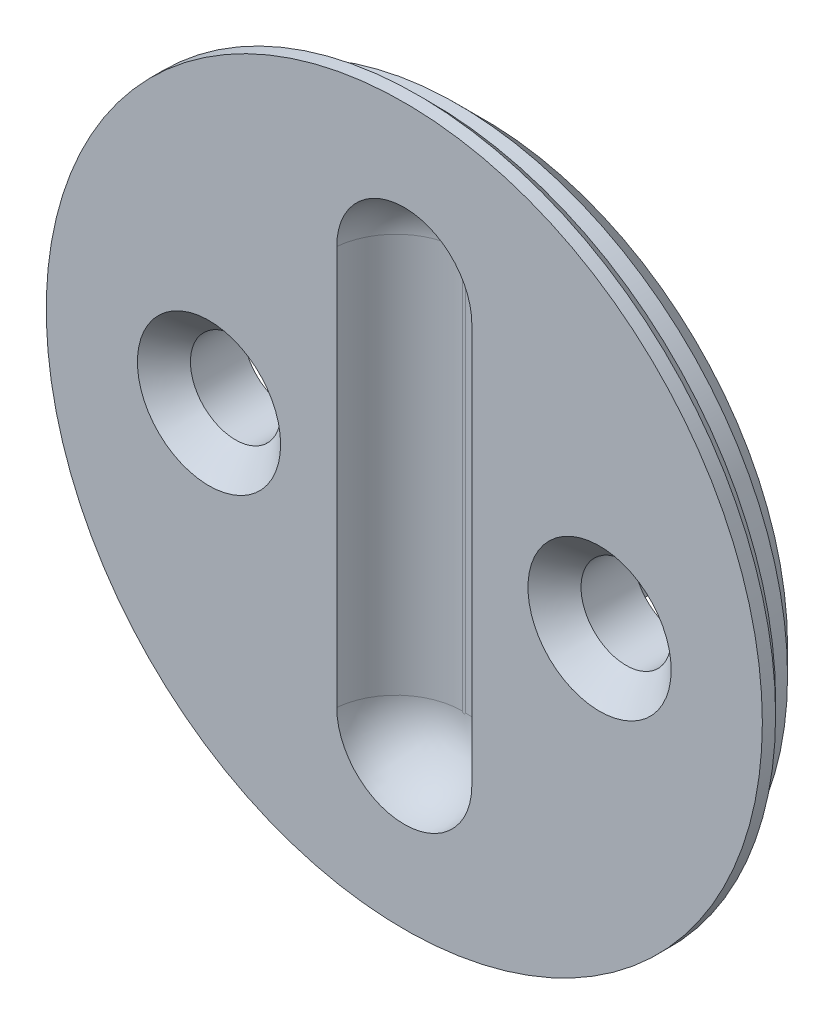
SolidWorks part; units mm, degrees
ref_plane "Front Plane" through (0, 0, 0) normal (0, 0, 1) x (1, 0, 0)
ref_plane "Top Plane" through (0, 0, 0) normal (0, 1, 0) x (1, 0, 0)
ref_plane "Right Plane" through (0, 0, 0) normal (1, 0, 0) x (0, 0, -1)
sketch "Sketch1" plane through (0, 0, 0) normal (0, 0, 1) x (1, 0, 0)
  line L0 (0, 9.3188) -> (0, -6.9028) construction
  circle A0 centre (0, 0) radius 12.45
  circle A1 centre (-7.363, 0) radius 1.7
  circle A2 centre (7.363, 0) radius 1.7
  dimension "D2" = 24.9
  dimension "D3" = 3.4
  dimension "D1" = 14.726
extrude "Boss-Extrude1" add sketch "Sketch1" against normal blind 2
sketch "Sketch2" plane through (0, 0, -2) normal (0, 0, -1) x (-1, 0, 0)
  line L1 (-3.85, 3.35) -> (3.85, 3.35)
  line L2 (-3.85, 3.35) -> (-3.85, -3.35)
  line L3 (-3.85, -3.35) -> (3.85, -3.35)
  line L4 (3.85, 3.35) -> (3.85, -3.35)
  line L5 (-3.85, 3.35) -> (3.85, -3.35) construction
  line L6 (-3.85, -3.35) -> (3.85, 3.35) construction
  point P0 (0, 0)
  dimension "D1" = 6.7
  dimension "D2" = 7.7
extrude "Boss-Extrude2" add sketch "Sketch2" along normal blind 3.5
sketch "Sketch3" plane through (0, 0, 0) normal (0, 0, 1) x (1, 0, 0)
  circle A0 centre (0, 0) radius 13.5
  circle A1 centre (-7.363, 0) radius 1.7
  circle A2 centre (7.363, 0) radius 1.7
  circle A3 centre (-7.363, 0) radius 1.7 construction
  dimension "D1" = 27
extrude "Boss-Extrude3" add sketch "Sketch3" along normal blind 1
chamfer "Chamfer1" distance 1 angle 45 5 edges at (0, 3.35, -5.5) (3.85, 0, -5.5) (0, -3.35, -5.5) (-3.85, 0, -5.5) (12.45, 0, -2)
chamfer "Chamfer2" distance 0.5 angle 45 1 edges at (13.5, 0, 0)
sketch "Sketch4" plane through (0, 0, 1) normal (0, 0, 1) x (1, 0, 0)
  line L0 (0, 7.5257) -> (0, -7.5257) construction
  line L1 (2.5463, 7.5257) -> (2.5463, -7.5257)
  line L2 (-2.5463, 7.5257) -> (-2.5463, -7.5257)
  arc A0 (2.5463, 7.5257) -> (-2.5463, 7.5257) centre (0, 7.5257) ccw
  arc A1 (-2.5463, -7.5257) -> (2.5463, -7.5257) centre (0, -7.5257) ccw
  point P2 (0, 0)
extrude "Cut-Extrude1" cut sketch "Sketch4" against normal blind 2.25
fillet "Fillet1" radius 2.5 4 edges at (-2.5463, 0, -1.25) (2.5463, 0, -1.25) (0, 10.0719, -1.25) (0, -10.0719, -1.25)
chamfer "Chamfer3" distance 1 angle 45 2 edges at (9.063, 0, 1) (-5.663, 0, 1)
